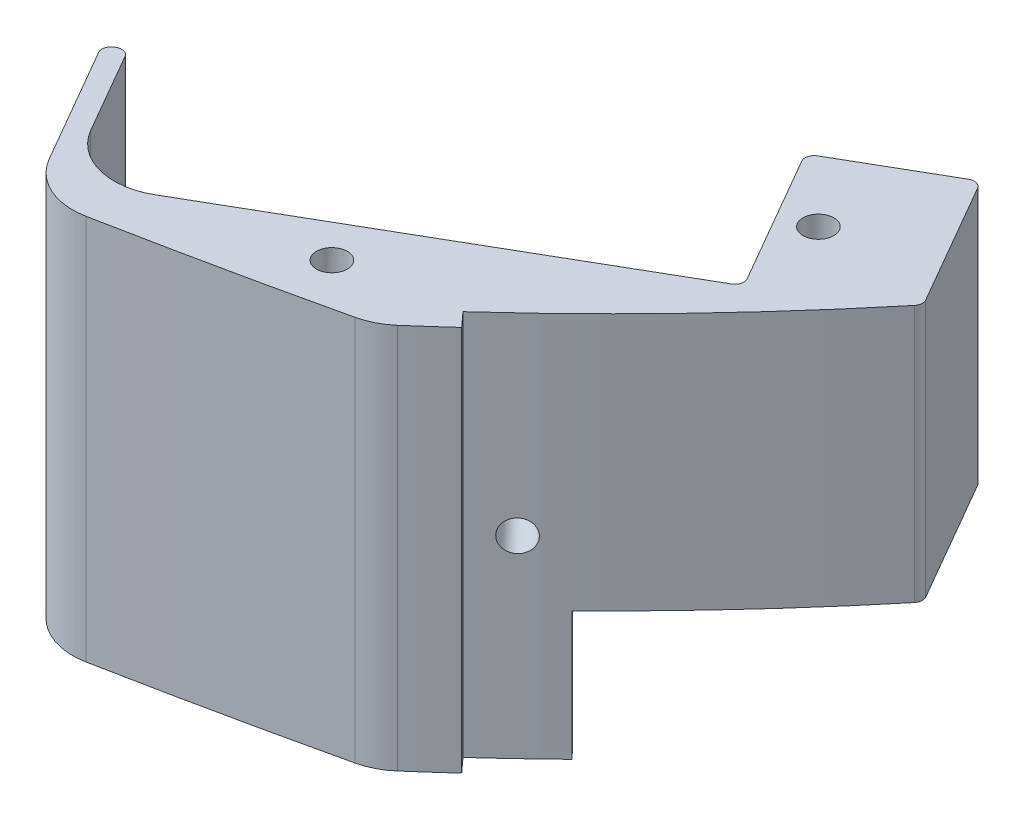
SolidWorks part; units mm, degrees
material "ABS"
ref_plane "Plan de face" through (0, 0, 0) normal (0, 0, 1) x (1, 0, 0)
ref_plane "Plan de dessus" through (0, 0, 0) normal (0, 1, 0) x (1, 0, 0)
ref_plane "Plan de droite" through (0, 0, 0) normal (1, 0, 0) x (0, 0, -1)
sketch "Esquisse1" plane through (0, 0, 0) normal (0, 1, 0) x (1, 0, 0)
  line L0 (112.1782, -122.5292) -> (105.6782, -111.2708) construction
  line L1 (84.0276, -123.7708) -> (92.6878, -118.7708)
  line L2 (84.0276, -123.7708) -> (91.4181, -136.5717)
  line L3 (0, 355) -> (0, 0) construction
  line L4 (92.6878, -118.7708) -> (99.1878, -130.0292)
  line L5 (118.6686, -103.7708) -> (127.3288, -98.7708)
  line L6 (118.6686, -103.7708) -> (125.1686, -115.0292)
  line L7 (125.1686, -115.0292) -> (99.1878, -130.0292)
  line L8 (127.3288, -98.7708) -> (134.2277, -110.72)
  line L9 (93.7728, -125.65) -> (124.0836, -108.15) construction
  circle A0 centre (93.7728, -125.65) radius 1.2
  circle A1 centre (124.0836, -108.15) radius 1.2
  arc A2 (91.4181, -136.5717) -> (113.4011, -131.9704) centre (0, 355) ccw
  arc A3 (113.4011, -131.9704) -> (134.2277, -110.72) centre (0, 0) ccw
  circle A4 centre (107.433, -129.3103) radius 1.2
  point P14 (102, -120.9)
  dimension "D1" = 35
  dimension "D2" = 2.4
  dimension "D3" = 500
  dimension "D4" = 174
  dimension "D6" = 6.5
  dimension "D7" = 9.5
  dimension "D9" = 10
  dimension "D15" = 10
  dimension "D16" = 7.5
  dimension "D17" = 26.9258
  dimension "D5" = 355
  dimension "D8" = 30
  dimension "D10" = 30
  dimension "D11" = 102
  dimension "D12" = 120.9
  dimension "D13" = 6.5
  dimension "D14" = 10
  dimension "D18" = 8
extrude "Boss.-Extru.1" add sketch "Esquisse1" along normal blind 20
sketch "Esquisse2" plane through (0, 20, 0) normal (0, 1, 0) x (1, 0, 0)
  line L0 (115.9914, -127.6803) -> (117, -128.7905)
  line L1 (134.2277, -110.72) -> (127.3288, -98.7708) construction
  line L2 (134.2277, -110.72) -> (133.4266, -109.3325)
  arc A0 (115.9914, -127.6803) -> (133.4266, -109.3325) centre (0, 0) ccw
  arc A1 (113.4011, -131.9704) -> (134.2277, -110.72) centre (0, 0) ccw construction
  arc A2 (117, -128.7905) -> (134.2277, -110.72) centre (0, 0) ccw
  dimension "D1" = 1.5
  dimension "D2" = 117
extrude "Enlèv. mat.-Extru.1" cut sketch "Esquisse2" against normal through all
hole_wizard "Diamètre du perçage Ø2.4 (2.4)1" positions "Esquisse3D1" profile "Esquisse3" hole size "Ø2.4" standard "ISO" end condition through all
sketch3d "Esquisse3D1"
  line L0 (115.9914, 0, 127.6803) -> (115.9914, 20, 127.6803) construction
  point P0 (118.1943, 5, 125.6438)
  dimension "D2" = 15
  dimension "D1" = 3
sketch "Esquisse3" plane through (118.1943, 5, 125.6438) normal (0, 1, 0) x (0.7284, 0, -0.6852)
  line L0 (0, 0) -> (0, 42.9839)
  line L1 (0, 42.9839) -> (1.2, 42.9839)
  line L2 (1.2, 42.9839) -> (1.2, 0)
  line L5 (1.2, 0) -> (0, 0)
  line L11 (0, -6.35) -> (0, 107.95) construction
  dimension "Diamètre du perçage jusqu'au prochain" = 2.4
  dimension "Profondeur du perçage jusqu'au prochain" = 42.9839
sketch "Esquisse4" plane through (0, 0, 0) normal (0, -1, 0) x (1, 0, 0)
  line L0 (84.0276, 123.7708) -> (91.4181, 136.5717) construction
  line L1 (115.9914, 127.6803) -> (117, 128.7905) construction
  line L2 (84.0276, 123.7708) -> (91.4181, 136.5717)
  line L3 (115.9914, 127.6803) -> (117, 128.7905)
  arc A0 (113.4011, 131.9704) -> (91.4181, 136.5717) centre (0, -355) ccw construction
  arc A1 (117, 128.7905) -> (113.4011, 131.9704) centre (0, 0) ccw construction
  arc A2 (133.4266, 109.3325) -> (115.9914, 127.6803) centre (0, 0) ccw construction
  arc A3 (113.4011, 131.9704) -> (91.4181, 136.5717) centre (0, -355) ccw
  arc A4 (117, 128.7905) -> (113.4011, 131.9704) centre (0, 0) ccw
  arc A5 (120.3616, 123.5692) -> (115.9914, 127.6803) centre (0, 0) ccw
  dimension "D1" = 6
extrude "Extru.-Mince1" add sketch "Esquisse4" along normal blind 10 thin
sketch "Esquisse5" plane through (0, 20, 0) normal (0, 1, 0) x (1, 0, 0)
  line L0 (112.1782, -122.5292) -> (91.8266, -134.2792)
  line L1 (112.1782, -122.5292) -> (105.6782, -111.2708)
  line L2 (91.8266, -134.2792) -> (85.3266, -123.0208)
  line L3 (105.6782, -111.2708) -> (85.3266, -123.0208)
  line L4 (125.1686, -115.0292) -> (99.1878, -130.0292) construction
  line L5 (92.6878, -118.7708) -> (84.0276, -123.7708) construction
  line L7 (84.0276, -123.7708) -> (91.4181, -136.5717) construction
  circle A0 centre (93.7728, -125.65) radius 1.2 construction
  dimension "D1" = 6
  dimension "D2" = 1.5
extrude "Enlèv. mat.-Extru.2" cut sketch "Esquisse5" against normal blind 10
fillet "Congé1" radius 0.7 12 edges at (84.0276, 5, 123.7708) (127.3288, 10, 98.7708) (133.4266, 10, 109.3325) (118.6686, 10, 103.7708) (92.6878, 5, 118.7708) (125.1686, 10, 115.0292) (99.1878, 5, 130.0292) (119.315, -5, 122.4946) (113.8681, -5, 127.5738) (114.8767, -5, 128.6841) (85.3266, 15, 123.0208)
fillet "Congé2" radius 5 6 edges at (113.4011, 5, 131.9704) (91.4181, 5, 136.5717) (92.1862, -5, 134.902) (112.7019, -5, 130.593) (91.8266, 15, 134.2792) (84.6771, -10, 123.3958)
